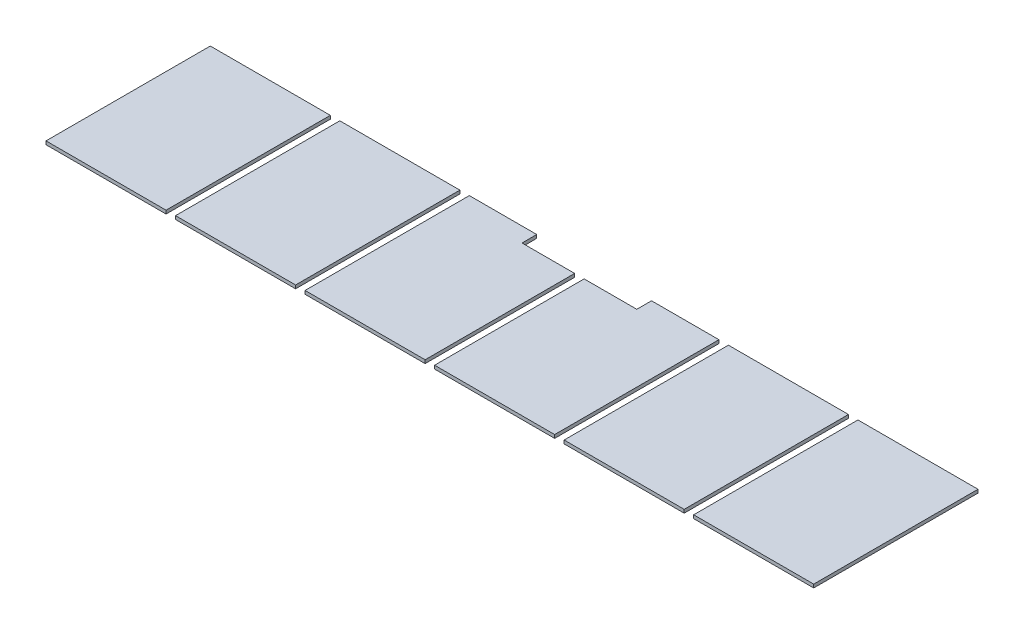
SolidWorks part; units mm, degrees
ref_plane "Front Plane" through (0, 0, 0) normal (0, 0, 1) x (1, 0, 0)
ref_plane "Top Plane" through (0, 0, 0) normal (0, 1, 0) x (1, 0, 0)
ref_plane "Right Plane" through (0, 0, 0) normal (1, 0, 0) x (0, 0, -1)
sketch "Sketch2" plane through (0, 0, 0) normal (0, 1, 0) x (1, 0, 0)
  line L4 (3073.4, 2044.7) -> (1625.6, 2044.7)
  line L5 (1625.6, 2044.7) -> (1625.6, 63.5)
  line L6 (1625.6, 63.5) -> (3073.4, 63.5)
  line L7 (3073.4, 63.5) -> (3073.4, 2044.7)
  line L8 (3073.4, 2044.7) -> (1625.6, 2044.7)
  line L9 (1625.6, 2044.7) -> (1625.6, 63.5)
  line L10 (1625.6, 63.5) -> (3073.4, 63.5)
  line L11 (3073.4, 63.5) -> (3073.4, 2044.7)
  line L12 (1511.3, 2044.7) -> (63.5, 2044.7)
  line L13 (63.5, 2044.7) -> (63.5, 63.5)
  line L14 (63.5, 63.5) -> (1511.3, 63.5)
  line L15 (1511.3, 63.5) -> (1511.3, 2044.7)
  line L16 (1511.3, 2044.7) -> (63.5, 2044.7)
  line L17 (63.5, 2044.7) -> (63.5, 63.5)
  line L18 (63.5, 63.5) -> (1511.3, 63.5)
  line L19 (1511.3, 63.5) -> (1511.3, 2044.7)
  line L20 (9321.8, 2044.7) -> (7874, 2044.7)
  line L21 (7874, 2044.7) -> (7874, 63.5)
  line L22 (7874, 63.5) -> (9321.8, 63.5)
  line L23 (9321.8, 63.5) -> (9321.8, 2044.7)
  line L24 (9321.8, 2044.7) -> (7874, 2044.7)
  line L25 (7874, 2044.7) -> (7874, 63.5)
  line L26 (7874, 63.5) -> (9321.8, 63.5)
  line L27 (9321.8, 63.5) -> (9321.8, 2044.7)
  line L28 (7759.7, 63.5) -> (7759.7, 2044.7)
  line L29 (6311.9, 63.5) -> (7759.7, 63.5)
  line L30 (6311.9, 2044.7) -> (6311.9, 63.5)
  line L31 (7759.7, 2044.7) -> (6311.9, 2044.7)
  line L32 (7759.7, 63.5) -> (7759.7, 2044.7)
  line L33 (6311.9, 63.5) -> (7759.7, 63.5)
  line L34 (6311.9, 2044.7) -> (6311.9, 63.5)
  line L35 (7759.7, 2044.7) -> (6311.9, 2044.7)
  line L36 (11976.1, 2298.7) -> (9436.1, 2298.7)
  line L37 (11976.1, 50.8) -> (11976.1, 2298.7)
  line L38 (6197.6, 2044.7) -> (5384.8, 2044.7)
  line L39 (6197.6, 63.5) -> (6197.6, 2044.7)
  line L40 (4749.8, 63.5) -> (6197.6, 63.5)
  line L41 (4749.8, 1866.9) -> (4749.8, 63.5)
  line L42 (5384.8, 1866.9) -> (4749.8, 1866.9)
  line L43 (5384.8, 2044.7) -> (5384.8, 1866.9)
  line L44 (6197.6, 2044.7) -> (5384.8, 2044.7)
  line L45 (6197.6, 63.5) -> (6197.6, 2044.7)
  line L46 (4749.8, 63.5) -> (6197.6, 63.5)
  line L47 (4749.8, 1866.9) -> (4749.8, 63.5)
  line L48 (5384.8, 1866.9) -> (4749.8, 1866.9)
  line L49 (5384.8, 2044.7) -> (5384.8, 1866.9)
  line L50 (3187.7, 2044.7) -> (3187.7, 63.5)
  line L51 (4000.5, 2044.7) -> (3187.7, 2044.7)
  line L52 (4000.5, 1866.9) -> (4000.5, 2044.7)
  line L53 (4635.5, 1866.9) -> (4000.5, 1866.9)
  line L54 (4635.5, 63.5) -> (4635.5, 1866.9)
  line L55 (3187.7, 63.5) -> (4635.5, 63.5)
  line L56 (3187.7, 2044.7) -> (3187.7, 63.5)
  line L57 (4000.5, 2044.7) -> (3187.7, 2044.7)
  line L58 (4000.5, 1866.9) -> (4000.5, 2044.7)
  line L59 (4635.5, 1866.9) -> (4000.5, 1866.9)
  line L60 (4635.5, 63.5) -> (4635.5, 1866.9)
  line L61 (3187.7, 63.5) -> (4635.5, 63.5)
  line L62 (9436.1, 50.8) -> (11976.1, 50.8)
  line L63 (9436.1, 2298.7) -> (9436.1, 50.8)
  line L64 (11976.1, 2298.7) -> (9436.1, 2298.7)
  line L65 (11976.1, 50.8) -> (11976.1, 2298.7)
  line L66 (9436.1, 50.8) -> (11976.1, 50.8)
  line L67 (9436.1, 2298.7) -> (9436.1, 50.8)
  dimension "D1" = 0
  dimension "D2" = 0
  dimension "D3" = 0
  dimension "D4" = 0
  dimension "D5" = 0
  dimension "D6" = 0
  dimension "D7" = 0
extrude "Boss-Extrude1" add sketch "Sketch2" along normal up to surface (40.64 mm away) contours L18 L19 L16 L17 | L10 L11 L8 L9 | L56 L61 L60 L59 L58 L57 | L44 L49 L48 L47 L46 L45 | L32 L35 L34 L33 | L26 L27 L24 L25 region at (2349.5, 0, -1054.1) region at (787.4, 0, -1054.1) region at (8597.9, 0, -1054.1) region at (7035.8, 0, -1054.1) region at (5490.3518, 0, -1017.1537) region at (3894.9482, 0, -1017.1537)
